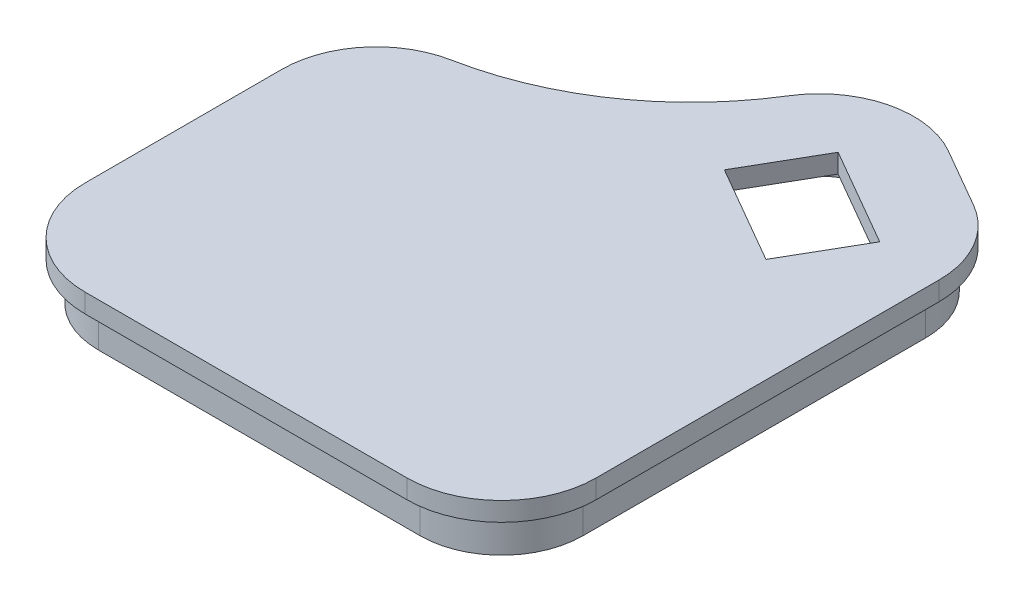
SolidWorks part; units mm, degrees
ref_plane "Front Plane" through (0, 0, 0) normal (0, 0, 1) x (1, 0, 0)
ref_plane "Top Plane" through (0, 0, 0) normal (0, 1, 0) x (1, 0, 0)
ref_plane "Right Plane" through (0, 0, 0) normal (1, 0, 0) x (0, 0, -1)
sketch "Sketch1" plane through (0, 0, 0) normal (0, 1, 0) x (1, 0, 0)
  line L1 (-130, 50) -> (130, 50)
  line L2 (-130, 50) -> (-130, -50)
  line L3 (-130, -50) -> (130, -50)
  line L4 (130, 50) -> (130, -50)
  line L5 (-130, 50) -> (130, -50) construction
  line L6 (-130, -50) -> (130, 50) construction
  point P0 (0, 0)
  dimension "D1" = 260
  dimension "D2" = 100
extrude "Boss-Extrude1" add sketch "Sketch1" along normal blind 3 contours L4 L3 L2 L1
sketch "Sketch4" plane through (0, 3, 0) normal (0, 1, 0) x (1, 0, 0)
  line L0 (-130, 50) -> (130, 50) construction
  line L1 (-77.5342, 30.2911) -> (-130, 0)
  line L2 (-130, 50) -> (-130, -50) construction
  line L3 (77.5342, 30.2911) -> (130, 0)
  line L4 (130, 50) -> (130, -50) construction
  line L5 (0, 0) -> (0, 50) construction
  line L6 (-130, -50) -> (130, -50) construction
  line L7 (-130, 0) -> (-130, 50)
  line L8 (-130, 50) -> (130, 50)
  line L9 (130, 50) -> (130, 0)
  arc A0 (-77.5342, 30.2911) -> (77.5342, 30.2911) centre (0, 50) ccw
  dimension "D1" = 160
  dimension "D2" = 60
  dimension "D3" = 60
  dimension "D4" = 50
extrude "Cut-Extrude1" cut sketch "Sketch4" against normal blind 5
sketch "Sketch5" plane through (0, 3, 0) normal (0, 1, 0) x (1, 0, 0)
  line L0 (-130, -50) -> (130, -50)
  line L1 (130, -50) -> (130, -130)
  line L2 (130, -130) -> (-130, -130)
  line L3 (-130, -130) -> (-130, -50)
  dimension "D1" = 80
extrude "Boss-Extrude4" add sketch "Sketch5" against normal blind 3
sketch "Sketch6" plane through (0, 3, 0) normal (0, 1, 0) x (1, 0, 0)
  line L6 (-79.3816, 25.7604) -> (-127, -1.7321)
  line L7 (-127, -1.7321) -> (-127, -127)
  line L8 (-127, -127) -> (127, -127)
  line L15 (127, -127) -> (127, -1.7321)
  line L16 (127, -1.7321) -> (79.3816, 25.7604)
  line L17 (-77.5342, 30.2911) -> (-130, 0)
  line L18 (-130, 0) -> (-130, -130)
  line L19 (-130, -130) -> (130, -130)
  line L20 (130, -130) -> (130, 0)
  line L27 (130, 0) -> (77.5342, 30.2911)
  line L28 (-77.5342, 30.2911) -> (-130, 0)
  line L29 (-130, 0) -> (-130, -130)
  line L30 (-130, -130) -> (130, -130)
  line L31 (130, -130) -> (130, 0)
  line L32 (130, 0) -> (77.5342, 30.2911)
  arc A3 (-79.3816, 25.7604) -> (79.3816, 25.7604) centre (0, 50) ccw
  arc A4 (-77.5342, 30.2911) -> (77.5342, 30.2911) centre (0, 50) ccw
  arc A5 (-77.5342, 30.2911) -> (77.5342, 30.2911) centre (0, 50) ccw
  dimension "D1" = 0
  dimension "D2" = 3
extrude "Boss-Extrude5" add sketch "Sketch6" along normal blind 70
sketch "Sketch7" plane through (0, 73, 0) normal (0, 1, 0) x (1, 0, 0)
  line L0 (-3.5, -32.9262) -> (-3.5, -130) construction
  line L2 (-5, -32.8493) -> (-5, -130)
  line L3 (-2, -32.9759) -> (-2, -130)
  line L4 (-2, -130) -> (-5, -130)
  line L5 (-5, 0) -> (-5, -130) construction
  line L6 (-3.5, 0) -> (-3.5, -130) construction
  line L7 (-2, 0) -> (-2, -130) construction
  line L8 (-130, -130) -> (130, -130) construction
  line L10 (-130, 0) -> (-130, -130) construction
  arc A2 (-79.3816, 25.7604) -> (79.3816, 25.7604) centre (0, 50) ccw construction
  arc A3 (-79.3816, 25.7604) -> (79.3816, 25.7604) centre (0, 50) ccw construction
  arc A4 (-5, -32.8493) -> (-2, -32.9759) centre (0, 50) ccw
  dimension "D3" = 125
  dimension "D1" = 1.5
  dimension "D2" = 1.5
extrude "Boss-Extrude6" add sketch "Sketch7" against normal up to surface (70 mm away)
sketch "Sketch9" plane through (0, 73, 0) normal (0, 1, 0) x (1, 0, 0)
  line L0 (-5, -32.8493) -> (-5, -144.8767)
  line L1 (-5, -144.8767) -> (-379.7281, -144.8767)
  line L2 (-379.7281, -144.8767) -> (-379.7281, 52.069)
  line L3 (-379.7281, 52.069) -> (-5, 52.069)
  line L4 (-5, 52.069) -> (-5, -32.8493)
extrude "Cut-Extrude3" cut sketch "Sketch9" against normal through all
sketch "Sketch10" plane through (0, 3, 0) normal (0, 1, 0) x (1, 0, 0)
  line L0 (130, -130) -> (130, 0) construction
  line L1 (14, -46.75) -> (86, -46.75) construction
  line L2 (14, -46.75) -> (14, -113.25) construction
  line L3 (14, -113.25) -> (86, -113.25) construction
  line L4 (86, -46.75) -> (86, -113.25) construction
  line L5 (14, -46.75) -> (86, -113.25) construction
  line L6 (14, -113.25) -> (86, -46.75) construction
  line L8 (-5, -130) -> (130, -130) construction
  circle A0 centre (14, -46.75) radius 5
  circle A1 centre (86, -46.75) radius 5
  circle A2 centre (86, -113.25) radius 5
  circle A3 centre (14, -113.25) radius 5
  circle A4 centre (14, -113.25) radius 1.75
  circle A5 centre (86, -113.25) radius 1.75
  circle A6 centre (14, -46.75) radius 1.75
  circle A7 centre (86, -46.75) radius 1.75
  point P0 (50, -80)
  dimension "D5" = 3.5
  dimension "D6" = 10
  dimension "D1" = 80
  dimension "D2" = 50
  dimension "D3" = 66.5
  dimension "D4" = 72
extrude "Boss-Extrude7" add sketch "Sketch10" along normal blind 50
chamfer "Chamfer1" distance 5 angle 60 4 edges at (86, 3, 108.25) (14, 3, 108.25) (86, 3, 41.75) (14, 3, 41.75)
fillet "Fillet1" radius 22 5 edges at (127, 38, 1.7321) (127, 38, 127) (-2, 38, 127) (-2, 38, 32.9759) (79.3816, 38, -25.7604)
fillet "Fillet2" radius 25 5 edges at (130, 36.5, 0) (77.5342, 36.5, -30.2911) (-5, 36.5, 29.8436) (-5, 36.5, 130) (130, 36.5, 130)
sketch "Sketch11" plane through (0, 3, 0) normal (0, 1, 0) x (1, 0, 0)
  line L1 (52.4643, -10.3946) -> (54.4317, -12.6594)
  line L4 (130, -105) -> (130, -14.4338)
  line L5 (117.5, 7.2169) -> (101.7371, 16.3176)
  line L6 (-5, -53.0776) -> (-5, -105)
  line L7 (20, -130) -> (105, -130)
  line L14 (15.2381, -28.5353) -> (15.8095, -31.4804)
  line L16 (101.7371, 16.3176) -> (100.2371, 13.7195)
  line L17 (100.2371, 13.7195) -> (116, 4.6188)
  line L18 (116, 4.6188) -> (117.5, 7.2169)
  line L19 (117.5, 7.2169) -> (101.7371, 16.3176)
  arc A0 (15.8095, -31.4804) -> (70.5398, 6.2606) centre (0, 50) ccw construction
  arc A1 (15.8095, -31.4804) -> (54.4317, -12.6594) centre (0, 50) ccw
  arc A8 (15.2381, -28.5353) -> (67.9902, 7.8415) centre (0, 50) ccw
  arc A9 (130, -14.4338) -> (117.5, 7.2169) centre (105, -14.4338) ccw
  arc A10 (101.7371, 16.3176) -> (67.9902, 7.8415) centre (89.2371, -5.333) ccw
  arc A11 (15.2381, -28.5353) -> (-5, -53.0776) centre (20, -53.0776) ccw
  arc A14 (15.2381, -28.5353) -> (52.4643, -10.3946) centre (0, 50) ccw
  arc A18 (-5, -105) -> (20, -130) centre (20, -105) ccw
  arc A19 (105, -130) -> (130, -105) centre (105, -105) ccw
  dimension "D2" = 30
  dimension "D1" = 0
extrude "Cut-Extrude4" cut sketch "Sketch11" along normal blind 20
sketch "Sketch12" plane through (0, 3, 0) normal (0, 1, 0) x (1, 0, 0)
  line L0 (105, -105) -> (15, -105) construction
  line L1 (15, -105) -> (15, -55) construction
  circle A0 centre (89.2371, -5.333) radius 1.75
  circle A1 centre (105, -105) radius 1.75
  circle A2 centre (15, -105) radius 1.75
  circle A3 centre (15, -55) radius 1.75
  dimension "D1" = 3.5
  dimension "D3" = 50
  dimension "D2" = 90
extrude "Cut-Extrude5" cut sketch "Sketch12" against normal blind 20
sketch "Sketch14" plane through (0, 23, 0) normal (0, -1, 0) x (1, 0, 0)
  line L4 (101.7371, -16.3176) -> (117.5, -7.2169)
  line L5 (117.5, -7.2169) -> (116, -4.6188)
  line L6 (116, -4.6188) -> (100.2371, -13.7195)
  line L7 (100.2371, -13.7195) -> (101.7371, -16.3176)
  line L8 (101.7371, -16.3176) -> (117.5, -7.2169)
  line L9 (117.5, -7.2169) -> (116, -4.6188)
  line L10 (116, -4.6188) -> (100.2371, -13.7195)
  line L11 (100.2371, -13.7195) -> (101.7371, -16.3176)
  dimension "D1" = 0
extrude "Cut-Extrude6" cut sketch "Sketch14" against normal blind 40
fillet "Fillet3" radius 5 8 edges at (53.448, 3, 11.527) (53.448, 23, 11.527) (15.5238, 23, 30.0079) (15.5238, 3, 30.0079) (100.9871, 63, -15.0186) (116.75, 63, -5.9178) (116.75, 3, -5.9178) (100.9871, 3, -15.0186)
sketch "Sketch15" plane through (0, 73, 0) normal (0, 1, 0) x (1, 0, 0)
  line L0 (126.5, -105) -> (126.5, -14.4338)
  line L1 (115.75, 4.1858) -> (99.9871, 13.2865)
  line L2 (-1.5, -53.0776) -> (-1.5, -105)
  line L3 (20, -126.5) -> (105, -126.5)
  line L4 (130, -105) -> (130, -14.4338)
  line L5 (117.5, 7.2169) -> (101.7371, 16.3176)
  line L6 (-5, -53.0776) -> (-5, -105)
  line L7 (20, -130) -> (105, -130)
  line L8 (130, -105) -> (130, -14.4338) construction
  line L9 (117.5, 7.2169) -> (101.7371, 16.3176) construction
  line L10 (-5, -53.0776) -> (-5, -105) construction
  line L11 (20, -130) -> (105, -130) construction
  line L12 (124.5, -105) -> (124.5, -14.4338)
  line L13 (114.75, 2.4537) -> (98.9871, 11.5545)
  line L14 (0.5, -53.0776) -> (0.5, -105)
  line L15 (20, -124.5) -> (105, -124.5)
  arc A0 (126.5, -14.4338) -> (115.75, 4.1858) centre (105, -14.4338) ccw
  arc A1 (99.9871, 13.2865) -> (70.9647, 5.9971) centre (89.2371, -5.333) ccw
  arc A2 (15.9048, -31.9713) -> (70.9647, 5.9971) centre (0, 50) ccw
  arc A3 (15.9048, -31.9713) -> (-1.5, -53.0776) centre (20, -53.0776) ccw
  arc A4 (-1.5, -105) -> (20, -126.5) centre (20, -105) ccw
  arc A5 (105, -126.5) -> (126.5, -105) centre (105, -105) ccw
  arc A6 (130, -14.4338) -> (117.5, 7.2169) centre (105, -14.4338) ccw
  arc A7 (101.7371, 16.3176) -> (67.9902, 7.8415) centre (89.2371, -5.333) ccw
  arc A8 (15.2381, -28.5353) -> (67.9902, 7.8415) centre (0, 50) ccw
  arc A9 (15.2381, -28.5353) -> (-5, -53.0776) centre (20, -53.0776) ccw
  arc A10 (-5, -105) -> (20, -130) centre (20, -105) ccw
  arc A11 (105, -130) -> (130, -105) centre (105, -105) ccw
  arc A12 (130, -14.4338) -> (117.5, 7.2169) centre (105, -14.4338) ccw construction
  arc A13 (101.7371, 16.3176) -> (67.9902, 7.8415) centre (89.2371, -5.333) ccw construction
  arc A14 (15.2381, -28.5353) -> (67.9902, 7.8415) centre (0, 50) ccw construction
  arc A15 (15.2381, -28.5353) -> (-5, -53.0776) centre (20, -53.0776) ccw construction
  arc A16 (-5, -105) -> (20, -130) centre (20, -105) ccw construction
  arc A17 (105, -130) -> (130, -105) centre (105, -105) ccw construction
  arc A18 (124.5, -14.4338) -> (114.75, 2.4537) centre (105, -14.4338) ccw
  arc A19 (98.9871, 11.5545) -> (72.6645, 4.9431) centre (89.2371, -5.333) ccw
  arc A20 (16.2857, -33.9347) -> (72.6645, 4.9431) centre (0, 50) ccw
  arc A21 (16.2857, -33.9347) -> (0.5, -53.0776) centre (20, -53.0776) ccw
  arc A22 (0.5, -105) -> (20, -124.5) centre (20, -105) ccw
  arc A23 (105, -124.5) -> (124.5, -105) centre (105, -105) ccw
  dimension "D1" = 0
  dimension "D2" = 3.5
  dimension "D3" = 2
extrude "Boss-Extrude8" add sketch "Sketch15" along normal blind 10 separate body
sketch "Sketch16" plane through (0, 0, 0) normal (0, 0, 1) x (1, 0, 0)
  line L0 (-5, 73) -> (130, 73)
  line L1 (130, 73) -> (130, 0)
  line L2 (130, 0) -> (-5, 0)
  line L3 (-5, 0) -> (-5, 73)
extrude "Cut-Extrude7" cut sketch "Sketch16" against normal through all both and the other way through all
sketch "Sketch17" plane through (0, 83, 0) normal (0, 1, 0) x (1, 0, 0)
  line L0 (130, -105) -> (130, -14.4338)
  line L1 (117.5, 7.2169) -> (101.7371, 16.3176)
  line L2 (-5, -53.0776) -> (-5, -105)
  line L3 (20, -130) -> (105, -130)
  line L4 (126.5, -105) -> (126.5, -14.4338)
  line L5 (115.75, 4.1858) -> (99.9871, 13.2865)
  line L6 (-1.5, -53.0776) -> (-1.5, -105)
  line L7 (20, -126.5) -> (105, -126.5)
  line L8 (126.5, -105) -> (126.5, -14.4338) construction
  line L9 (115.75, 4.1858) -> (99.9871, 13.2865) construction
  line L10 (-1.5, -53.0776) -> (-1.5, -105) construction
  line L11 (20, -126.5) -> (105, -126.5) construction
  arc A0 (130, -14.4338) -> (117.5, 7.2169) centre (105, -14.4338) ccw
  arc A1 (101.7371, 16.3176) -> (67.9902, 7.8415) centre (89.2371, -5.333) ccw
  arc A2 (15.2381, -28.5353) -> (67.9902, 7.8415) centre (0, 50) ccw
  arc A3 (15.2381, -28.5353) -> (-5, -53.0776) centre (20, -53.0776) ccw
  arc A4 (-5, -105) -> (20, -130) centre (20, -105) ccw
  arc A5 (105, -130) -> (130, -105) centre (105, -105) ccw
  arc A6 (105, -126.5) -> (126.5, -105) centre (105, -105) ccw
  arc A7 (126.5, -14.4338) -> (115.75, 4.1858) centre (105, -14.4338) ccw
  arc A8 (99.9871, 13.2865) -> (70.9647, 5.9971) centre (89.2371, -5.333) ccw
  arc A9 (15.9048, -31.9713) -> (70.9647, 5.9971) centre (0, 50) ccw
  arc A10 (15.9048, -31.9713) -> (-1.5, -53.0776) centre (20, -53.0776) ccw
  arc A11 (-1.5, -105) -> (20, -126.5) centre (20, -105) ccw
  arc A12 (105, -126.5) -> (126.5, -105) centre (105, -105) ccw construction
  arc A13 (126.5, -14.4338) -> (115.75, 4.1858) centre (105, -14.4338) ccw construction
  arc A14 (99.9871, 13.2865) -> (70.9647, 5.9971) centre (89.2371, -5.333) ccw construction
  arc A15 (15.9048, -31.9713) -> (70.9647, 5.9971) centre (0, 50) ccw construction
  arc A16 (15.9048, -31.9713) -> (-1.5, -53.0776) centre (20, -53.0776) ccw construction
  arc A17 (-1.5, -105) -> (20, -126.5) centre (20, -105) ccw construction
  dimension "D1" = 0
  dimension "D2" = 3.5
extrude "Boss-Extrude9" add sketch "Sketch17" along normal blind 5
sketch "Sketch18" plane through (0, 88, 0) normal (0, 1, 0) x (1, 0, 0)
  line L0 (87.4519, 1.4711) -> (113.4327, -13.5289)
  line L1 (113.4327, -13.5289) -> (102.4327, -32.5814)
  line L2 (102.4327, -32.5814) -> (76.4519, -17.5814)
  line L3 (76.4519, -17.5814) -> (87.4519, 1.4711)
  line L4 (117.5, 7.2169) -> (101.7371, 16.3176) construction
  arc A0 (15.2381, -28.5353) -> (67.9902, 7.8415) centre (0, 50) ccw construction
  dimension "D1" = 30
  dimension "D2" = 22
  dimension "D3" = 20
  dimension "D4" = 100
extrude "Cut-Extrude8" cut sketch "Sketch18" against normal blind 5
